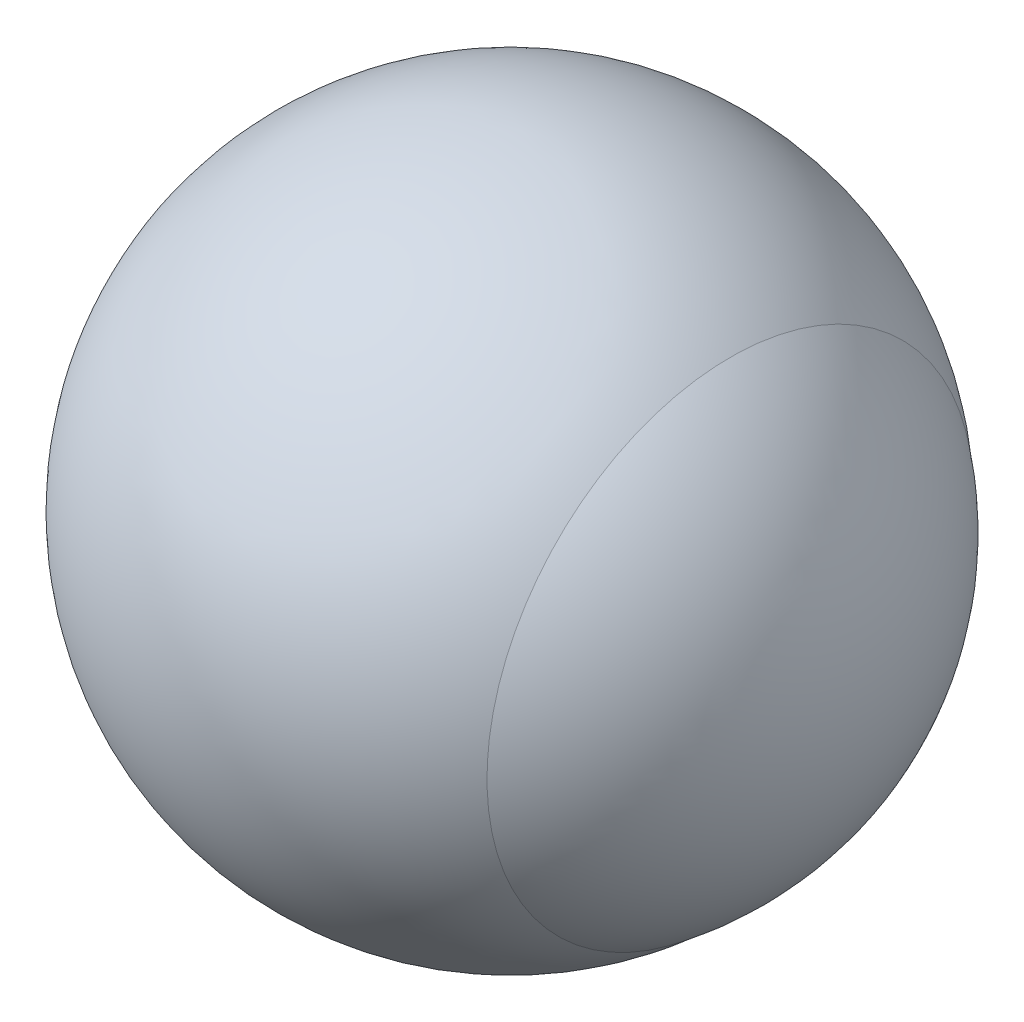
SolidWorks part; units mm, degrees
other "Камера1"
ref_plane "Спереди" through (0, 0, 0) normal (0, 0, 1) x (1, 0, 0)
ref_plane "Сверху" through (0, 0, 0) normal (0, 1, 0) x (1, 0, 0)
ref_plane "Справа" through (0, 0, 0) normal (1, 0, 0) x (0, 0, -1)
sketch "Эскиз2" plane through (0, 0, 0) normal (0, 1, 0) x (1, 0, 0)
  line L1 (13.435, -13.435) -> (-13.435, -13.435)
  line L2 (13.435, -13.435) -> (13.435, 13.435)
  line L3 (13.435, 13.435) -> (-13.435, 13.435)
  line L4 (-13.435, -13.435) -> (-13.435, 13.435)
  line L5 (13.435, -13.435) -> (-13.435, 13.435) construction
  line L6 (13.435, 13.435) -> (-13.435, -13.435) construction
  point P0 (0, 0)
  dimension "D1" = 38
  dimension "D2" = 26.8701
ref_plane "Плоскость1" through (0, 26.8701, 0) normal (0, 1, 0) x (1, 0, 0)
ref_plane "Плоскость2" through (0, 0, -13.435) normal (0, 0, 1) x (1, 0, 0)
ref_plane "Плоскость3" through (-13.435, 0, 0) normal (1, 0, 0) x (0, 0, -1)
sketch "Эскиз5" plane through (-13.435, 0, 0) normal (1, 0, 0) x (0, 0, -1)
  line L0 (-10.565, 26.8701) -> (37.435, 26.8701)
  line L1 (26.4, 26.8701) -> (-26.4, 26.8701) construction
  line L2 (-10.565, 26.8701) -> (37.435, 26.8701) construction
  arc A0 (37.435, 26.8701) -> (-10.565, 26.8701) centre (13.435, 26.8701) ccw
  point P0 (13.435, 26.8701)
  dimension "D1" = 24
revolve "Повернуть1" add sketch "Эскиз5" angle 360 about L2
extrude "Бобышка-Вытянуть1" [suppressed] add sketch "Эскиз2" along normal blind 26.87
pattern_linear "Линейный массив1" [suppressed] count 2 spacing 26.87 count 2 spacing 26.87 of bodies 108
sketch "Эскиз6" plane through (0, 0, -13.435) normal (0, 0, 1) x (1, 0, 0)
  line L0 (26.4, 26.8701) -> (-26.4, 26.8701) construction
  line L1 (11.565, 26.8701) -> (10.565, 26.8701) construction
  line L2 (11.565, 26.8701) -> (10.565, 26.8701)
  arc A0 (11.565, 26.8701) -> (2.6646, 44.669) centre (-10.6823, 26.8701) ccw
  arc A1 (10.565, 26.8701) -> (2.6646, 44.669) centre (-13.435, 26.8701) ccw
  circle A2 centre (-13.435, 26.8701) radius 24 construction
  dimension "D1" = 1
revolve "Повернуть5" add sketch "Эскиз6" angle 360 about L1
other "Сечение1" [suppressed]
other "Сечение3" [suppressed]
other "Сечение7" [suppressed]
ref_axis "Ось1" through (-13.435, 28.0701, -13.435) along (0, -1, 0)
equation "\"x\"= \"D2@Эскиз2\""
equation "\"half\"= \"D2@Эскиз2\" / 2"
